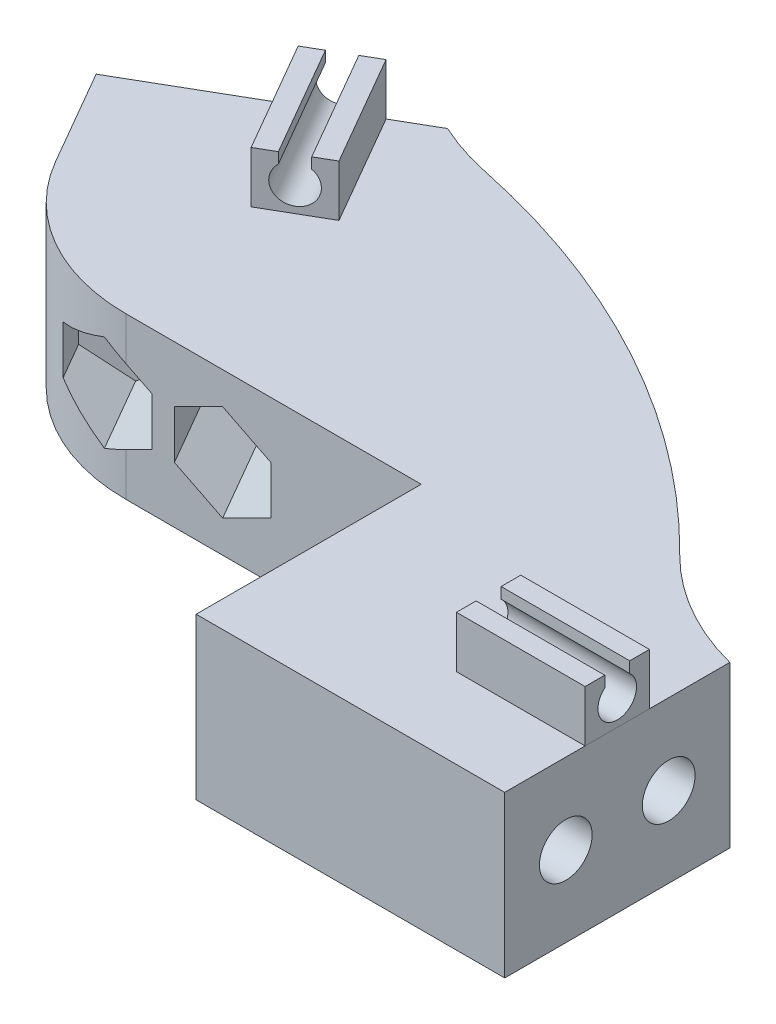
SolidWorks part; units mm, degrees
ref_plane "Спереди" through (0, 0, 0) normal (0, 0, 1) x (1, 0, 0)
ref_plane "Сверху" through (0, 0, 0) normal (0, 1, 0) x (1, 0, 0)
ref_plane "Справа" through (0, 0, 0) normal (1, 0, 0) x (0, 0, -1)
sketch "Sketch1" plane through (0, 0, 0) normal (0, 1, 0) x (1, 0, 0)
  line L0 (-61.4249, 58.3949) -> (-23.9249, -6.5571)
  line L1 (-23.9249, -6.5571) -> (67.0559, -6.5571)
  line L2 (67.0559, -6.5571) -> (67.0559, 28.4429)
  line L3 (67.0559, 28.4429) -> (2.0559, 28.4429)
  line L4 (2.0559, 28.4429) -> (-26.7838, 78.3949)
  line L5 (-26.7838, 78.3949) -> (-61.4249, 58.3949)
  dimension "D1" = 120
  dimension "D2" = 40
  dimension "D3" = 65
  dimension "D4" = 75
  dimension "D5" = 35
extrude "Boss-Extrude1" add sketch "Sketch1" along normal blind 25
sketch "Sketch2" plane through (67.0559, 0, 0) normal (1, 0, 0) x (0, 0, -1)
  line L0 (28.4429, 12.5) -> (-6.5571, 12.5) construction
  line L1 (28.4429, 25) -> (28.4429, 0) construction
  line L2 (-6.5571, 25) -> (-6.5571, 0) construction
  circle A0 centre (2.9429, 12.5) radius 4.1
  circle A1 centre (18.9429, 12.5) radius 4.1
  circle A2 centre (2.9429, 12.5) radius 8 construction
  circle A3 centre (18.9429, 12.5) radius 8 construction
  point P12 (10.9429, 12.5)
  dimension "D1" = 8.2
  dimension "D3" = 16
  dimension "D2" = 16
  dimension "D4" = 8
extrude "Cut-Extrude1" cut sketch "Sketch2" against normal through all
sketch "Sketch3" plane through (-40.6419, 0, -70.3939) normal (-0.5, 0, -0.866) x (-0.866, 0, 0.5)
  line L0 (-16.0019, 12.5) -> (23.9981, 12.5) construction
  line L3 (-16.0019, 25) -> (-16.0019, 0) construction
  line L4 (23.9981, 25) -> (23.9981, 0) construction
  circle A0 centre (-4.0019, 12.5) radius 4.1
  circle A1 centre (11.9981, 12.5) radius 4.1
  point P8 (3.9981, 12.5)
  dimension "D1" = 8.2
  dimension "D2" = 16
  dimension "D3" = 8
extrude "Cut-Extrude2" cut sketch "Sketch3" against normal through all
sketch "Sketch5" plane through (-40.6419, 0, -70.3939) normal (-0.5, 0, -0.866) x (-0.866, 0, 0.5)
  line L1 (-10.4971, 16.25) -> (-10.4971, 8.75)
  line L2 (-10.4971, 8.75) -> (-4.0019, 5)
  line L3 (-4.0019, 5) -> (2.4933, 8.75)
  line L4 (2.4933, 8.75) -> (2.4933, 16.25)
  line L5 (2.4933, 16.25) -> (-4.0019, 20)
  line L6 (-4.0019, 20) -> (-10.4971, 16.25)
  line L7 (-16.0019, 25) -> (-16.0019, 0) construction
  line L8 (5.5029, 8.75) -> (11.9981, 5)
  line L9 (11.9981, 5) -> (18.4933, 8.75)
  line L10 (18.4933, 8.75) -> (18.4933, 16.25)
  line L11 (18.4933, 16.25) -> (11.9981, 20)
  line L12 (11.9981, 20) -> (5.5029, 16.25)
  line L13 (5.5029, 16.25) -> (5.5029, 8.75)
  circle A0 centre (-4.0019, 12.5) radius 7.5 construction
  circle A1 centre (11.9981, 12.5) radius 7.5 construction
  dimension "D1" = 15
extrude "Cut-Extrude4" cut sketch "Sketch5" against normal through all from offset 28 offset against normal yes
chamfer "Chamfer1" distance 56 angle 30 1 edges at (2.0559, 12.5, -28.4429) first distance on face at (34.5559, 12.5, -28.4429)
sketch "Sketch6" plane through (0, 0, 0) normal (0, -1, 0) x (1, 0, 0)
  line L0 (-0.9249, 6.5571) -> (-0.9249, -28.4429)
  line L1 (-23.9249, 6.5571) -> (67.0559, 6.5571) construction
  line L2 (-0.9249, -28.4429) -> (-44.1321, -28.4429)
  line L3 (-61.4249, -58.3949) -> (-23.9249, 6.5571) construction
  line L4 (-0.9249, 6.5571) -> (-23.9249, 6.5571)
  line L5 (-23.9249, 6.5571) -> (-44.1321, -28.4429)
  line L6 (67.0559, 6.5571) -> (67.0559, -28.4429) construction
  dimension "D1" = 23
extrude "Cut-Extrude5" cut sketch "Sketch6" against normal through all
sketch "Sketch7" plane through (-40.6419, 0, -70.3939) normal (-0.5, 0, -0.866) x (-0.866, 0, 0.5)
  line L0 (-4.0019, 16.6) -> (-4.0019, 39.225) construction
  line L2 (-16.0019, 25) -> (23.9981, 25) construction
  line L3 (0.9981, 33) -> (-9.0019, 33) construction
  line L4 (0.9981, 33) -> (0.9981, 25)
  line L5 (0.9981, 25) -> (-9.0019, 25)
  line L6 (-9.0019, 33) -> (-9.0019, 25)
  line L7 (0.9981, 33) -> (-9.0019, 25) construction
  line L8 (0.9981, 25) -> (-9.0019, 33) construction
  line L9 (-9.0019, 33) -> (-5.9019, 33)
  line L10 (-5.9019, 33) -> (-5.9019, 31.3216)
  line L11 (-5.9019, 31.3216) -> (-2.1019, 31.3216) construction
  line L13 (-2.1019, 31.3216) -> (-2.1019, 33)
  line L14 (-2.1019, 33) -> (0.9981, 33)
  circle A1 centre (-4.0019, 12.5) radius 4.1 construction
  circle A2 centre (-4.0019, 29) radius 3 construction
  arc A3 (-5.9019, 31.3216) -> (-2.1019, 31.3216) centre (-4.0019, 29) ccw
  point P4 (-4.0019, 29)
  dimension "D3" = 6
  dimension "D1" = 8
  dimension "D2" = 10
  dimension "D4" = 3.8
extrude "Boss-Extrude2" add sketch "Sketch7" against normal blind 20
sketch "Sketch8" plane through (67.0559, 0, 0) normal (1, 0, 0) x (0, 0, -1)
  line L0 (10.9429, 25) -> (10.9429, 46.5452) construction
  line L2 (-6.5571, 25) -> (28.4429, 25) construction
  line L3 (5.9429, 33) -> (9.0026, 33)
  line L4 (5.9429, 33) -> (15.9429, 33) construction
  line L5 (5.9429, 33) -> (5.9429, 25)
  line L6 (5.9429, 25) -> (15.9429, 25)
  line L7 (15.9429, 33) -> (15.9429, 25)
  line L8 (5.9429, 33) -> (15.9429, 25) construction
  line L9 (5.9429, 25) -> (15.9429, 33) construction
  line L10 (9.0026, 33) -> (9.0026, 31.288)
  line L11 (9.0026, 31.288) -> (12.8833, 31.288) construction
  line L12 (12.8833, 31.288) -> (12.8833, 33)
  line L13 (12.8833, 33) -> (15.9429, 33)
  circle A0 centre (10.9429, 29) radius 3 construction
  arc A1 (9.0026, 31.288) -> (12.8833, 31.288) centre (10.9429, 29) ccw
  point P4 (10.9429, 29)
  dimension "D3" = 10
  dimension "D1" = 6
  dimension "D2" = 8
extrude "Boss-Extrude3" add sketch "Sketch8" against normal blind 20 separate body
sketch "Sketch9" plane through (0, 25, 0) normal (0, 1, 0) x (1, 0, 0)
  line L0 (19.0751, -6.5571) -> (19.0751, 28.4429)
  line L1 (-0.9249, -6.5571) -> (67.0559, -6.5571) construction
  line L2 (19.0751, 28.4429) -> (-0.9249, 28.4429)
  line L3 (-0.9249, 28.4429) -> (-0.9249, -6.5571)
  line L4 (-0.9249, -6.5571) -> (19.0751, -6.5571)
  dimension "D1" = 20
extrude "Cut-Extrude6" cut sketch "Sketch9" against normal through all
sketch "Sketch10" plane through (0, 25, 0) normal (0, 1, 0) x (1, 0, 0)
  line L0 (58.0559, 28.4429) -> (-25.9441, 76.9404)
  arc A0 (-25.9441, 76.9404) -> (58.0559, 28.4429) centre (-45.3281, -53.6286) cw
  dimension "D1" = 132
extrude "Boss-Extrude4" add sketch "Sketch10" against normal up to surface (25 mm away) up to face at (8.0037, 0, -34.932)
fillet "Fillet1" radius 40 2 edges at (-25.9441, 12.5, -76.9404) (58.0559, 12.5, -28.4429)
fillet "Fillet2" radius 30 1 edges at (-44.1321, 12.5, -28.4429)
